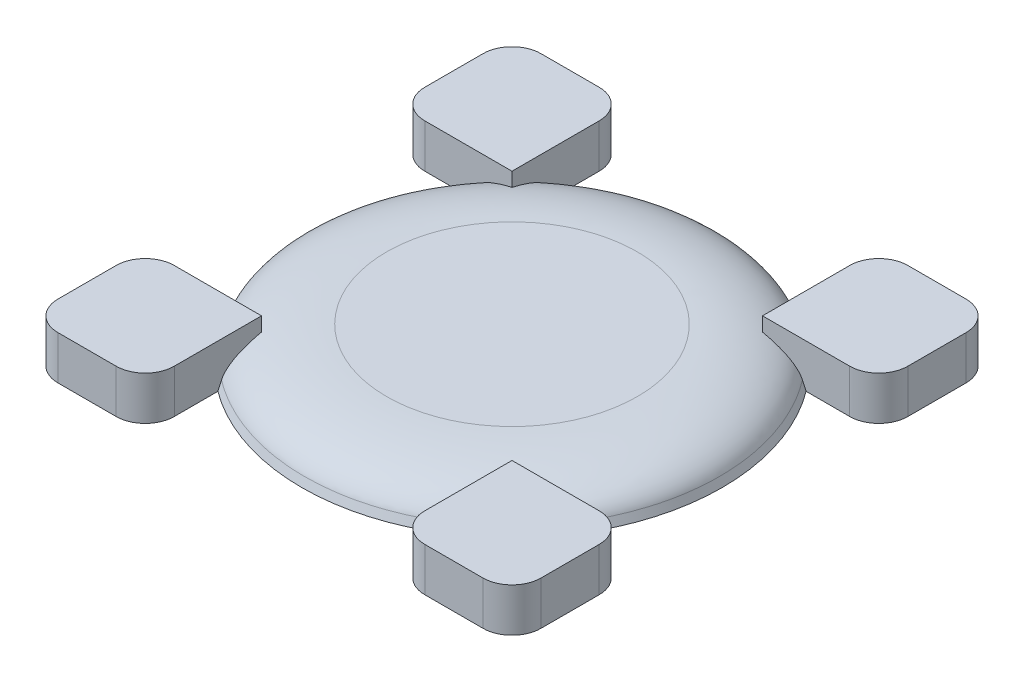
SolidWorks part; units mm, degrees
material "ABS"
ref_plane "Front Plane" through (0, 0, 0) normal (0, 0, 1) x (1, 0, 0)
ref_plane "Top Plane" through (0, 0, 0) normal (0, 1, 0) x (1, 0, 0)
ref_plane "Right Plane" through (0, 0, 0) normal (1, 0, 0) x (0, 0, -1)
sketch "Sketch1" plane through (0, 0, 0) normal (0, 1, 0) x (1, 0, 0)
  line L1 (-17.5, 17.5) -> (17.5, 17.5)
  line L2 (-17.5, 17.5) -> (-17.5, -17.5)
  line L3 (-17.5, -17.5) -> (17.5, -17.5)
  line L4 (17.5, 17.5) -> (17.5, -17.5)
  line L5 (-17.5, 17.5) -> (17.5, -17.5) construction
  line L6 (-17.5, -17.5) -> (17.5, 17.5) construction
  point P0 (0, 0)
  dimension "D1" = 35
sketch "Sketch2" plane through (0, 0, 0) normal (0, 1, 0) x (1, 0, 0)
  circle A0 centre (0, 0) radius 14.4638
extrude "Boss-Extrude1" add sketch "Sketch2" along normal blind 2.5 draft 20
fillet "Fillet1" radius 4 1 edges at (0, 2.5, 13.5539) second distance 6 first distance on face at (0, 2.5, 13.5539)
sketch "Sketch4" plane through (0, 0, 0) normal (0, 1, 0) x (1, 0, 0)
  line L0 (-17.5, -17.5) -> (17.5, 17.5) construction
  line L1 (-16.6164, -16.6164) -> (-8.6164, -16.6164)
  line L2 (-16.6164, -16.6164) -> (-16.6164, -8.6164)
  line L3 (-16.6164, -8.6164) -> (-8.6164, -8.6164)
  line L4 (-8.6164, -16.6164) -> (-8.6164, -8.6164)
  line L5 (-16.6164, -16.6164) -> (-8.6164, -8.6164) construction
  line L6 (-16.6164, -8.6164) -> (-8.6164, -16.6164) construction
  point P0 (-12.6164, -12.6164)
  dimension "D1" = 8
extrude "Boss-Extrude2" add sketch "Sketch4" along normal blind 3
fillet "Fillet2" radius 2 3 edges at (-8.6164, 1.5, 16.6164) (-16.6164, 1.5, 16.6164) (-16.6164, 1.5, 8.6164)
pattern_circular "CirPattern1" count 4 over 360 about axis through (0, 0, 0) along (0, 1, 0) of "Fillet2", "Boss-Extrude2"
